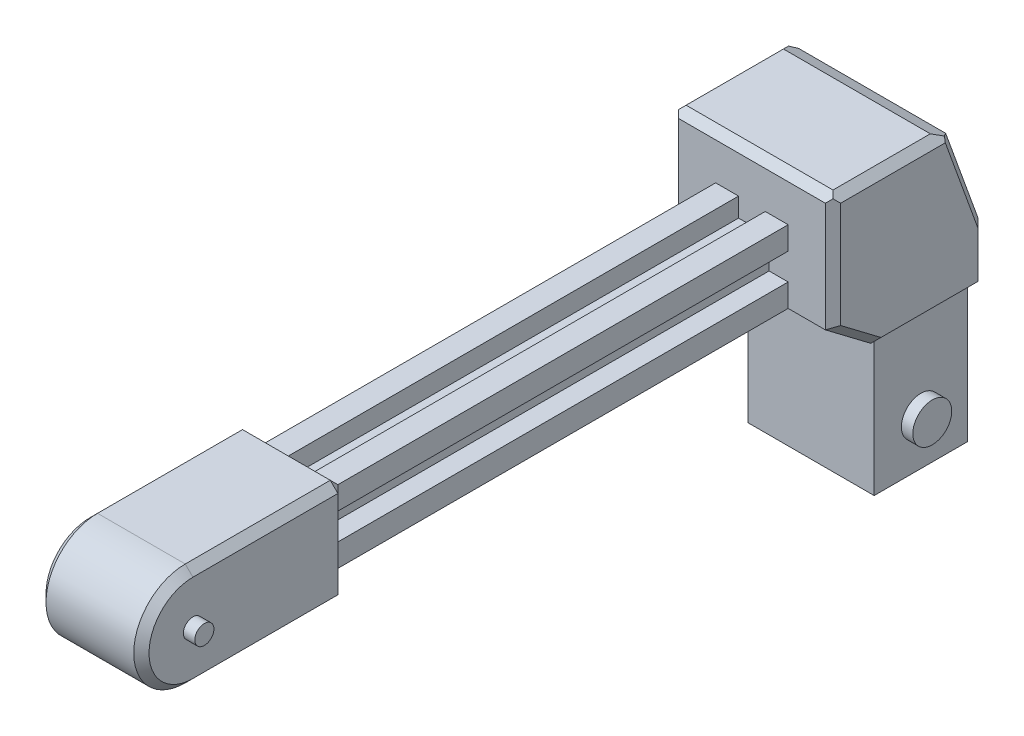
SolidWorks part; units mm, degrees
ref_plane "前视基准面" through (0, 0, 0) normal (0, 0, 1) x (1, 0, 0)
ref_plane "上视基准面" through (0, 0, 0) normal (0, 1, 0) x (1, 0, 0)
ref_plane "右视基准面" through (0, 0, 0) normal (1, 0, 0) x (0, 0, -1)
sketch "草图1" plane through (0, 0, 0) normal (1, 0, 0) x (0, 0, -1)
  line L1 (0, 0) -> (200, 0)
  line L2 (0, 0) -> (0, 19)
  line L3 (0, 19) -> (200, 19)
  line L4 (200, 0) -> (200, 19)
  dimension "D1" = 200
  dimension "D2" = 19
extrude "凸台-拉伸1" add sketch "草图1" along normal blind 19
sketch "草图2" plane through (19, 0, 0) normal (1, 0, 0) x (0, 0, -1)
  line L0 (0, 19) -> (0, 0) construction
  line L1 (0, 19) -> (0, 0)
  arc A0 (0, 19) -> (0, 0) centre (0, 9.5) ccw
sketch "草图6" plane through (0, 0, 0) normal (0, 0, 1) x (1, 0, 0)
  line L0 (0, 9.5) -> (19, 9.5) construction
  line L1 (0, 19) -> (0, 0) construction
  line L2 (19, 0) -> (19, 19) construction
  line L3 (9.5, 19) -> (9.5, 0) construction
  line L4 (19, 19) -> (0, 19) construction
  line L5 (19, 0) -> (0, 0) construction
  line L7 (-4, -4) -> (23, -4)
  line L8 (-4, -4) -> (-4, 23)
  line L9 (-4, 23) -> (23, 23)
  line L10 (23, -4) -> (23, 23)
  line L11 (-4, -4) -> (23, 23) construction
  line L12 (-4, 23) -> (23, -4) construction
  point P12 (9.5, 9.5)
  dimension "D1" = 27
  dimension "D2" = 27
extrude "凸台-拉伸6" add sketch "草图6" against normal blind 40
sketch "草图7" plane through (23, 0, 0) normal (1, 0, 0) x (0, 0, -1)
  line L0 (0, 19) -> (0, 0) construction
  line L1 (0, -4) -> (0, 23)
  arc A0 (0, 23) -> (0, -4) centre (0, 9.5) ccw
extrude "凸台-拉伸7" add sketch "草图7" against normal up to surface (27 mm away) up to face at (-4, 9.5, -20)
sketch "草图8" plane through (0, 0, -200) normal (0, 0, -1) x (-1, 0, 0)
  line L0 (-19, 9.5) -> (0, 9.5) construction
  line L1 (-19, 19) -> (-19, 0) construction
  line L2 (0, 19) -> (0, 0) construction
  line L3 (-9.5, 19) -> (-9.5, 0) construction
  line L4 (0, 19) -> (-19, 19) construction
  line L5 (-19, 0) -> (0, 0) construction
  line L7 (-30.75, -11.75) -> (11.75, -11.75)
  line L8 (-30.75, -11.75) -> (-30.75, 30.75)
  line L9 (-30.75, 30.75) -> (11.75, 30.75)
  line L10 (11.75, -11.75) -> (11.75, 30.75)
  line L11 (-30.75, -11.75) -> (11.75, 30.75) construction
  line L12 (-30.75, 30.75) -> (11.75, -11.75) construction
  point P12 (-9.5, 9.5)
  dimension "D1" = 42.5
  dimension "D2" = 42.5
extrude "凸台-拉伸8" add sketch "草图8" against normal blind 40
sketch "草图9" plane through (23, 0, 0) normal (1, 0, 0) x (0, 0, -1)
  line L0 (0, 19) -> (0, 0) construction
  circle A0 centre (0, 9.5) radius 2.5
  dimension "D1" = 5
extrude "凸台-拉伸9" add sketch "草图9" along normal blind 3
sketch "草图10" plane through (-4, 0, 0) normal (-1, 0, 0) x (0, 0, 1)
  line L0 (0, 19) -> (0, 0) construction
  circle A0 centre (0, 9.5) radius 2.5
  dimension "D1" = 5
extrude "凸台-拉伸10" add sketch "草图10" along normal blind 3
sketch "草图11" plane through (0, -11.75, 0) normal (0, -1, 0) x (1, 0, 0)
  line L0 (30.75, -200) -> (-11.75, -200) construction
  line L1 (26, -200) -> (-7, -200)
  line L2 (26, -200) -> (26, -175.5383)
  line L3 (26, -175.5383) -> (-7, -175.5383)
  line L4 (-7, -200) -> (-7, -175.5383)
  line L5 (9.5, -175.5383) -> (9.5, -200) construction
  line L6 (9.5, -160) -> (9.5, -200) construction
  line L7 (0, -160) -> (19, -160) construction
  dimension "D1" = 33
extrude "凸台-拉伸11" add sketch "草图11" along normal blind 35
sketch "草图12" plane through (30.75, 0, 0) normal (1, 0, 0) x (0, 0, -1)
  line L0 (160, 0) -> (175.5383, -11.75)
  line L1 (160, -11.75) -> (200, -11.75) construction
  line L2 (175.5383, -46.75) -> (175.5383, -11.75) construction
  line L3 (175.5383, -11.75) -> (160, -11.75)
  line L4 (160, -11.75) -> (160, 0)
extrude "切除-拉伸1" cut sketch "草图12" against normal up to surface (42.5 mm away) up to face at (-11.75, 9.5, -180)
sketch "草图13" plane through (-11.75, 0, 0) normal (-1, 0, 0) x (0, 0, 1)
  line L0 (-190.8391, 30.75) -> (-200, 5.411)
  line L1 (-160, 30.75) -> (-200, 30.75) construction
  line L2 (-200, -11.75) -> (-200, 30.75) construction
  line L3 (-200, 5.411) -> (-200, 30.75)
  line L4 (-200, 30.75) -> (-190.8391, 30.75)
extrude "切除-拉伸2" cut sketch "草图13" against normal up to surface (42.5 mm away) up to face at (30.75, 7.6, -179.1077)
sketch "草图14" plane through (0, 0, -200) normal (0, 0, -1) x (-1, 0, 0)
  line L0 (-26, -11.75) -> (-30.75, -7)
  line L1 (-30.75, 5.411) -> (-30.75, -11.75) construction
  line L2 (-30.75, -7) -> (-30.75, -11.75)
  line L3 (-30.75, -11.75) -> (-26, -11.75)
  line L4 (7, -11.75) -> (11.75, -7)
  line L5 (11.75, -11.75) -> (11.75, 5.411) construction
  line L6 (11.75, -7) -> (11.75, -11.75)
  line L7 (7, -11.75) -> (11.75, -11.75) construction
  line L8 (11.75, -11.75) -> (7, -11.75)
  dimension "D1" = 45
  dimension "D2" = 45
extrude "切除-拉伸3" cut sketch "草图14" against normal up to surface (30.7431 mm away) up to face at (9.5, -5.875, -167.7691)
sketch "草图15" plane through (0, 0, 0) normal (-1, 0, 0) x (0, 0, 1)
  line L0 (-160, 9.5) -> (-40, 9.5) construction
  line L1 (-160, 0) -> (-160, 19) construction
  line L2 (-40, 23) -> (-40, -4) construction
  line L3 (-40, 19) -> (-40, 0) construction
  line L4 (-40, 13) -> (-160, 13)
  line L5 (-40, 13) -> (-40, 6)
  line L6 (-40, 6) -> (-160, 6)
  line L7 (-160, 13) -> (-160, 6)
  line L8 (-40, 9.5) -> (-160, 9.5) construction
  dimension "D1" = 7
extrude "切除-拉伸4" cut sketch "草图15" against normal blind 5
sketch "草图16" plane through (19, 0, 0) normal (1, 0, 0) x (0, 0, -1)
  line L0 (40, -4) -> (40, 23) construction
  line L1 (40, 13) -> (160, 13)
  line L2 (40, 13) -> (40, 6)
  line L3 (40, 6) -> (160, 6)
  line L4 (160, 13) -> (160, 6)
  line L5 (160, 30.75) -> (160, 0) construction
  line L6 (40, 9.5) -> (110.7117, 9.5)
  line L7 (40, 9.5) -> (101.9301, 9.5)
  line L8 (40, 19) -> (40, 0) construction
  dimension "D1" = 7
extrude "切除-拉伸5" cut sketch "草图16" against normal blind 5 contours L2 L3 L1 region at (19, 11.798, -100)
sketch "草图17" plane through (0, 0, 0) normal (0, -1, 0) x (1, 0, 0)
  line L0 (19, -40) -> (0, -40) construction
  line L1 (6, -40) -> (13, -40)
  line L2 (6, -40) -> (6, -160)
  line L3 (6, -160) -> (13, -160)
  line L4 (13, -40) -> (13, -160)
  line L5 (0, -160) -> (19, -160) construction
  line L6 (9.5, -40) -> (9.5, -77.3026)
  line L7 (9.5, -160) -> (9.5, -109.9423)
  line M8 (0, -160) -> (19, -160)
  line M10 (19, -40) -> (0, -40)
  dimension "D1" = 7
extrude "切除-拉伸6" cut sketch "草图17" against normal blind 5 contours L4 L1 L2 L3 M10 M8 region at (9.5, 0, -100)
sketch "草图18" plane through (0, 19, 0) normal (0, 1, 0) x (1, 0, 0)
  line L0 (-11.75, 160) -> (30.75, 160) construction
  line L1 (6, 160) -> (13, 160)
  line L2 (6, 160) -> (6, 40)
  line L3 (6, 40) -> (13, 40)
  line L4 (13, 160) -> (13, 40)
  line L5 (0, 40) -> (19, 40) construction
  line L6 (9.5, 40) -> (9.5, 44.0403)
  line L7 (9.5, 40) -> (9.5, 49.1059)
  line L8 (9.5, 40) -> (9.5, 47.2552) construction
  dimension "D1" = 7
extrude "切除-拉伸7" cut sketch "草图18" against normal blind 5 contours L4 L2 L3 region at (9.5, 19, -100)
chamfer "倒角1" distance 2 angle 45 5 edges at (30.75, -0.7945, -200) (30.75, 18.0805, -195.4196) (30.75, 30.75, -175.4196) (30.75, -3.5, -164.6284) (30.75, 15.375, -160)
chamfer "倒角2" distance 2 angle 45 5 edges at (-11.75, -0.7945, -200) (-11.75, -3.5, -164.6284) (-11.75, 15.375, -160) (-11.75, 30.75, -175.4196) (-11.75, 18.0805, -195.4196)
chamfer "倒角3" distance 2 angle 45 2 edges at (9.5, 30.75, -190.8391) (9.5, 30.75, -160) first distance on face at (9.5, 18.0805, -195.4196) first distance on face at (9.5, 12.075, -160)
chamfer "倒角4" distance 2 angle 45 10 edges at (-4, -4, -20) (23, -4, -20) (-4, 9.5, 13.5) (23, 9.5, 13.5) (23, 9.5, -40) (9.5, -4, -40) (-4, 9.5, -40) (-4, 23, -20) (9.5, 23, -40) (23, 23, -20)
sketch "Sketch2" plane through (-7, 0, 0) normal (-1, 0, 0) x (0, 0, 1)
  line L5 (-200, -46.75) -> (-175.5383, -46.75) construction
  arc A4 (-183.0691, -32.7701) -> (-192.4691, -32.7701) centre (-187.7691, -34.75) cw
  circle A5 centre (-187.7691, -34.75) radius 5.1
  point P15 (-187.7691, -46.75)
  dimension "D2" = 5.1
  dimension "D1" = 12
extrude "Boss-Extrude1" add sketch "Sketch2" along normal blind 3 contours A4 A5 region at (-7, -34.75, -187.7691)
sketch "Sketch3" plane through (26, 0, 0) normal (1, 0, 0) x (0, 0, -1)
  line L0 (200, -46.75) -> (175.5383, -46.75) construction
  arc A0 (192.4691, -32.7701) -> (183.0691, -32.7701) centre (187.7691, -34.75) cw
  circle A1 centre (187.7691, -34.75) radius 5.1
  point P6 (187.7691, -46.75)
  dimension "D1" = 10.2
  dimension "D2" = 12
extrude "Boss-Extrude2" add sketch "Sketch3" along normal blind 3 contours A0 A1 region at (26, -34.75, -187.7691)
ref_axis "Axis1" through (-2, 9.5, 0) along (1, 0, 0)
ref_plane "Plane2" through (9.5, 0, 0) normal (1, 0, 0) x (0, 0, -1)
ref_point "Point5"
ref_axis "Axis2" through (-34.6538, -34.75, -187.7691) along (1, 0, 0)
ref_plane "Plane3" through (9.5, 0, 0) normal (1, 0, 0) x (0, 0, -1)
ref_point "Point6"
